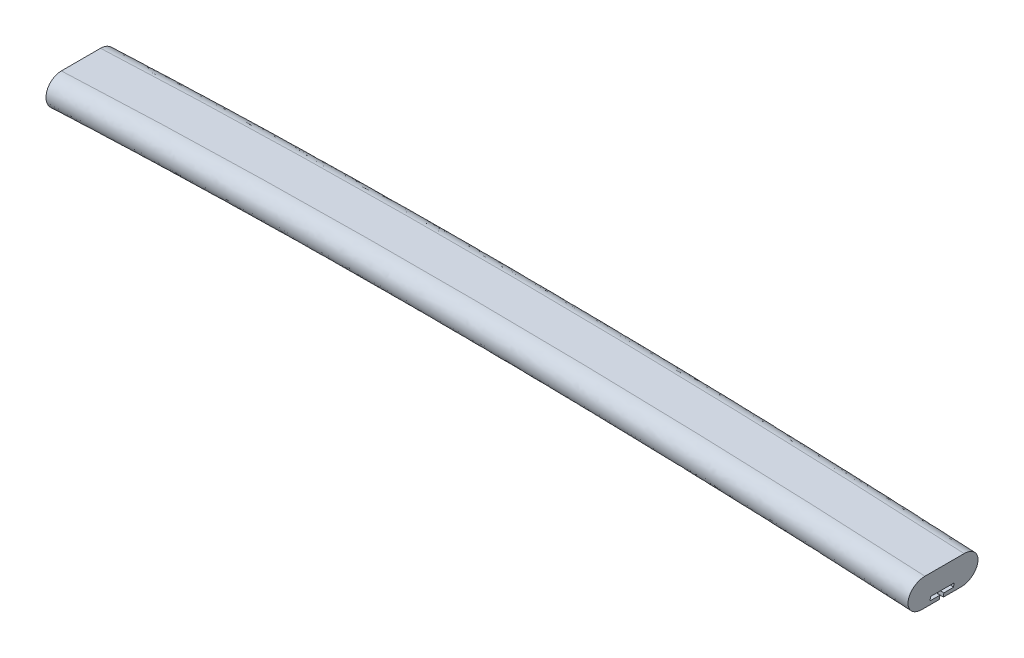
SolidWorks part; units mm, degrees
ref_plane "Front Plane" through (0, 0, 0) normal (0, 0, 1) x (1, 0, 0)
ref_plane "Top Plane" through (0, 0, 0) normal (0, 1, 0) x (1, 0, 0)
ref_plane "Right Plane" through (0, 0, 0) normal (1, 0, 0) x (0, 0, -1)
sketch "Sketch2" plane through (0, 0, 0) normal (1, 0, 0) x (0, 0, -1)
  line L0 (0, 0) -> (0, 28.6008) construction
  line L1 (0, 28.6008) -> (50, 28.6008) construction
  line L2 (0, 48.1481) -> (50, 48.1481)
  line L3 (0, 9.0535) -> (50, 9.0535)
  arc A0 (0, 48.1481) -> (0, 9.0535) centre (0, 28.6008) ccw
  arc A1 (50, 9.0535) -> (50, 48.1481) centre (50, 28.6008) ccw
  point P3 (25, 28.6008)
  dimension "D1" = 50
sketch3d "3DSketch1"
  line L0 (0, 28.6008, 0) -> (0, 28.6008, -50) construction
  spline S0 degree 2 poles (0, 28.6008, -25) (515.5195, 52.925, -25) (1099.5087, 21.3273, -25) knots 0 0 0 1 1 1
  dimension "D1" = 1100
sweep "Sweep1" add profiles "Sketch2" path "3DSketch1"
sketch "Sketch3" plane through (0, 0, 0) normal (-1, 0, 0) x (0, 0, 1)
  line L0 (-25, 9.0535) -> (-25, 19.0535) construction
  line L1 (0, 9.0535) -> (-50, 9.0535) construction
  line L2 (-40, 19.0535) -> (-10, 19.0535)
  line L3 (-10, 19.0535) -> (-10, 14.0535)
  line L4 (-10, 14.0535) -> (-22.5, 14.0535)
  line L5 (-22.5, 14.0535) -> (-22.5, 9.0535)
  line L6 (0, 9.0535) -> (-50, 9.0535) construction
  line L7 (-27.5, 14.0535) -> (-27.5, 9.0535)
  line L8 (-40, 14.0535) -> (-27.5, 14.0535)
  line L9 (-40, 19.0535) -> (-40, 14.0535)
  line L11 (-27.5, 9.0535) -> (-27.5, 5.2264)
  line L12 (-27.5, 5.2264) -> (-22.1748, 5.2264)
  line L13 (-22.1748, 5.2264) -> (-22.5, 9.0535)
sweep "Cut-Sweep1" cut profiles "Sketch3" path "3DSketch1<2>"
sketch3d "3DSketch1<2>" same geometry as "3DSketch1"
